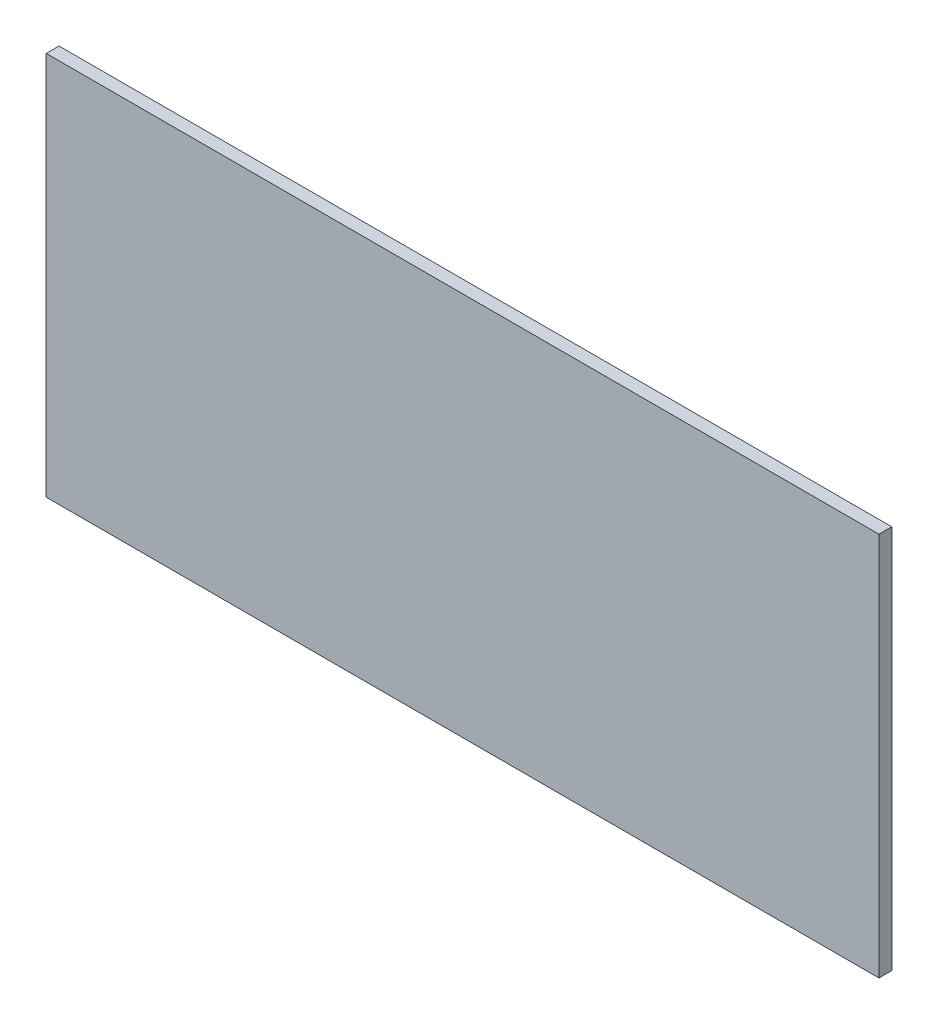
SolidWorks part; units mm, degrees
ref_plane "Front Plane" through (0, 0, 0) normal (0, 0, 1) x (1, 0, 0)
ref_plane "Top Plane" through (0, 0, 0) normal (0, 1, 0) x (1, 0, 0)
ref_plane "Right Plane" through (0, 0, 0) normal (1, 0, 0) x (0, 0, -1)
sketch "Sketch1" plane through (0, 0, 0) normal (0, 0, 1) x (1, 0, 0)
  line L0 (125.9407, 9.445) -> (125.9407, -9.555) construction
  line L1 (100.9407, 9.445) -> (150.9407, 9.445) construction
  line L2 (150.9407, -9.555) -> (100.9407, -9.555) construction
  line L3 (93.4407, 14.945) -> (93.4407, -15.055) construction
  line L5 (158.4407, -15.055) -> (158.4407, 14.945) construction
  line L6 (158.4407, 14.945) -> (93.4407, 14.945) construction
  line L7 (93.4407, 14.945) -> (93.4407, -15.055) construction
  line L8 (158.4407, -15.055) -> (93.4407, 14.945) construction
  line L9 (158.4407, 14.945) -> (93.4407, -15.055) construction
  line L12 (158.4407, 14.945) -> (93.4407, 14.945) construction
  line L13 (93.4407, -15.055) -> (93.4407, 14.945)
  line L14 (93.4407, 14.945) -> (158.4407, 14.945)
  line L15 (158.4407, 14.945) -> (158.4407, -15.055)
  line L16 (158.4407, -15.055) -> (93.4407, -15.055)
  point P6 (125.9407, -0.055)
  dimension "D1" = 65
  dimension "D2" = 30
extrude "Boss-Extrude1" add sketch "Sketch1" against normal blind 1
sketch "Sketch2" plane through (0, 0, -1) normal (0, 0, -1) x (-1, 0, 0)
  line L0 (-150.9407, 6.945) -> (-100.9407, 6.945) construction
  line L1 (-150.9407, -9.555) -> (-150.9407, 9.445) construction
  line L2 (-100.9407, -9.555) -> (-100.9407, 9.445) construction
  line L3 (-150.9407, -7.055) -> (-100.9407, -7.055) construction
  line L4 (-103.4407, 9.445) -> (-103.4407, -9.555) construction
  line L5 (-100.9407, 9.445) -> (-150.9407, 9.445) construction
  line L6 (-150.9407, -9.555) -> (-100.9407, -9.555) construction
  line L7 (-148.4407, 9.445) -> (-148.4407, -9.555) construction
  line L8 (-148.4407, 9.445) -> (-103.4407, 9.445)
  line L9 (-100.9407, 6.945) -> (-100.9407, -7.055)
  line L10 (-103.4407, -9.555) -> (-148.4407, -9.555)
  line L12 (-150.9407, -7.055) -> (-150.9407, 6.945)
  arc A0 (-150.9407, 6.945) -> (-148.4407, 9.445) centre (-148.4407, 6.945) cw
  arc A1 (-103.4407, 9.445) -> (-100.9407, 6.945) centre (-103.4407, 6.945) cw
  arc A2 (-103.4407, -9.555) -> (-100.9407, -7.055) centre (-103.4407, -7.055) ccw
  arc A3 (-148.4407, -9.555) -> (-150.9407, -7.055) centre (-148.4407, -7.055) cw
  dimension "D1" = 2.5
extrude "Boss-Extrude2" add sketch "Sketch2" along normal blind 1 separate body
